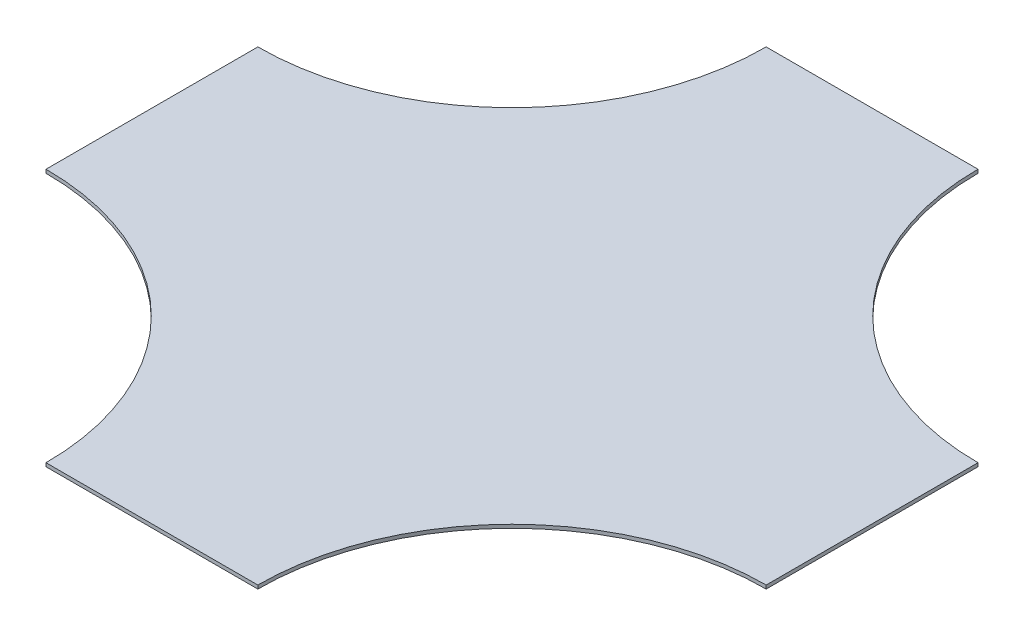
SolidWorks part; units mm, degrees
ref_plane "Front Plane" through (0, 0, 0) normal (0, 0, 1) x (1, 0, 0)
ref_plane "Top Plane" through (0, 0, 0) normal (0, 1, 0) x (1, 0, 0)
ref_plane "Right Plane" through (0, 0, 0) normal (1, 0, 0) x (0, 0, -1)
sketch "Sketch1" plane through (0, 0, 0) normal (0, 1, 0) x (1, 0, 0)
  line L1 (-95.25, -323.85) -> (95.25, -323.85)
  line L2 (-323.85, -95.25) -> (-323.85, 95.25)
  line L3 (-95.25, 323.85) -> (95.25, 323.85)
  line L4 (323.85, -95.25) -> (323.85, 95.25)
  line L5 (-162.2054, -162.2054) -> (162.2054, 162.2054) construction
  line L6 (-162.2054, 162.2054) -> (162.2054, -162.2054) construction
  arc A0 (-323.85, 95.25) -> (-95.25, 323.85) centre (-323.85, 323.85) ccw
  arc A1 (95.25, 323.85) -> (323.85, 95.25) centre (323.85, 323.85) ccw
  arc A2 (-95.25, -323.85) -> (-323.85, -95.25) centre (-323.85, -323.85) ccw
  arc A3 (323.85, -95.25) -> (95.25, -323.85) centre (323.85, -323.85) ccw
  point P0 (0, 0)
  dimension "D3" = 457.2
  dimension "D4" = 457.2
  dimension "D5" = 457.2
  dimension "D6" = 457.2
  dimension "D1" = 647.7
  dimension "D2" = 647.7
extrude "Boss-Extrude1" add sketch "Sketch1" along normal blind 3.175
